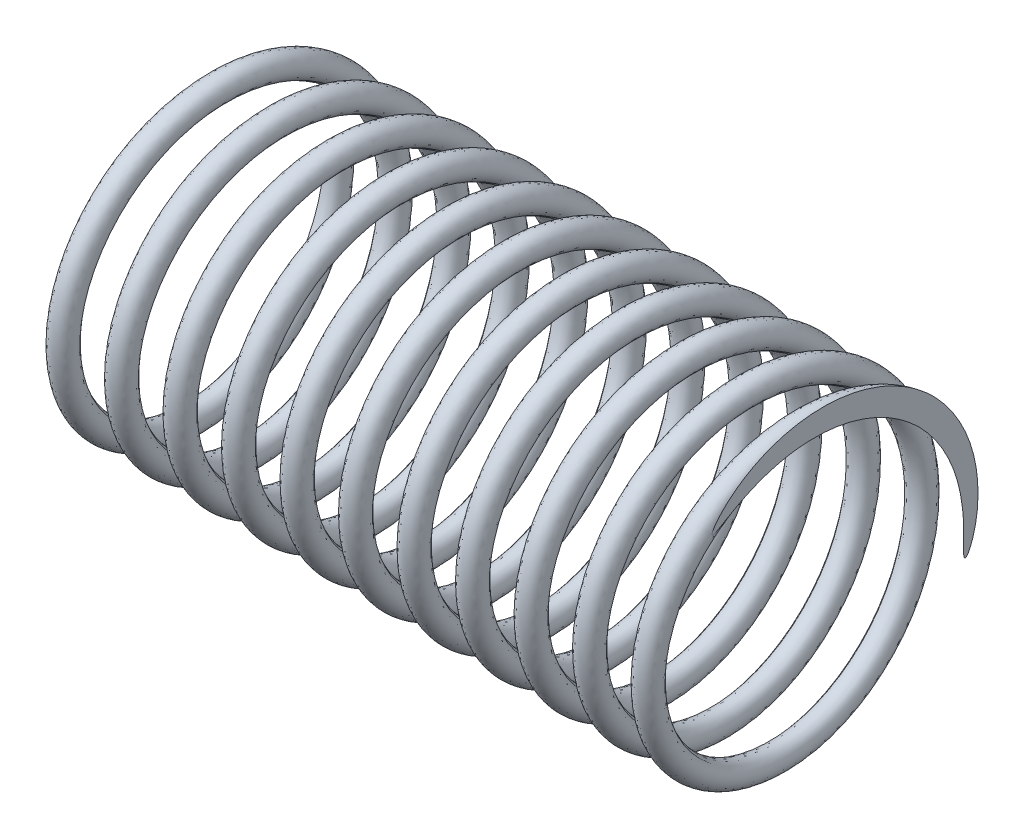
SolidWorks part; units mm, degrees
note: '?' marks a value the reader was unsure of.
material "SPRING STEEL ASTM A 229"
ref_plane "Front Plane" through (0, 0, 0) normal (0, 0, 1) x (1, 0, 0)
ref_plane "Top Plane" through (0, 0, 0) normal (0, 1, 0) x (1, 0, 0)
ref_plane "Right Plane" through (0, 0, 0) normal (1, 0, 0) x (0, 0, -1)
sketch "Sketch1" plane through (0, 0, 0) normal (1, 0, 0) x (0, 0, -1)
  circle A0 centre (0, 0) radius 3.1
  dimension "D1" = 6.2
curve "Helix/Spiral1" pitch 1.2 height 26 turns 21.6667
sketch "Sketch2" plane through (0, 0, 0) normal (0, 1, 0) x (1, 0, 0)
  circle A0 centre (0, 3.1) radius 0.25
  spline S0 degree 3 poles (0, 3.1) (0.0249, 3.1) (0.0752, 2.938) (0.1503, 2.2459) (0.2254, 1.2106) (0.3006, -0.0096) (0.3757, -1.2284) (0.4509, -2.2595) (0.526, -2.9453) (0.6012, -3.181) (0.6763, -2.9305) (0.7514, -2.2322) (0.8266, -1.1928) (0.9017, 0.0289) (0.9769, 1.2462) (1.052, 2.273) (1.1272, 2.9525) (1.2023, 3.1808) (1.2775, 2.923) (1.3526, 2.2185) (1.4277, 1.1749) (1.5029, -0.0481) (1.578, -1.2639) (1.6532, -2.2865) (1.7283, -2.9596) (1.8035, -3.1805) (1.8786, -2.9153) (1.9538, -2.2046) (2.0289, -1.157) (2.104, 0.0674) (2.1792, 1.2815) (2.2543, 2.2998) (2.3295, 2.9666) (2.4046, 3.1801) (2.4798, 2.9076) (2.5549, 2.1907) (2.6301, 1.1391) (2.7052, -0.0866) (2.7803, -1.2991) (2.8555, -2.3131) (2.9306, -2.9735) (3.0058, -3.1796) (3.0809, -2.8997) (3.1561, -2.1767) (3.2312, -1.1211) (3.3064, 0.1059) (3.3815, 1.3167) (3.4566, 2.3262) (3.5318, 2.9803) (3.6069, 3.1789) (3.6821, 2.8917) (3.7572, 2.1626) (3.8324, 1.103) (3.9075, -0.1251) (3.9827, -1.3342) (4.0578, -2.3393) (4.1329, -2.987) (4.2081, -3.1782) (4.2832, -2.8837) (4.3584, -2.1485) (4.4335, -1.085) (4.5087, 0.1444) (4.5838, 1.3516) (4.659, 2.3523) (4.7341, 2.9935) (4.8092, 3.1773) (4.8844, 2.8755) (4.9595, 2.1342) (5.0347, 1.0668) (5.1098, -0.1636) (5.185, -1.369) (5.2601, -2.3652) (5.3353, -3) (5.4104, -3.1763) (5.4855, -2.8672) (5.5607, -2.1199) (5.6358, -1.0487) (5.711, 0.1828) (5.7861, 1.3864) (5.8613, 2.3781) (5.9364, 3.0064) (6.0116, 3.1752) (6.0867, 2.8588) (6.1618, 2.1055) (6.237, 1.0305) (6.3121, -0.202) (6.3873, -1.4037) (6.4624, -2.3908) (6.5376, -3.0126) (6.6127, -3.174) (6.6879, -2.8503) (6.763, -2.0911) (6.8382, -1.0122) (6.9133, 0.2213) (6.9884, 1.4209) (7.0636, 2.4035) (7.1387, 3.0187) (7.2139, 3.1726) (7.289, 2.8417) (7.3642, 2.0765) (7.4393, 0.994) (7.5145, -0.2405) (7.5896, -1.4381) (7.6647, -2.4161) (7.7399, -3.0247) (7.815, -3.1712) (7.8902, -2.833) (7.9653, -2.0619) (8.0405, -0.9757) (8.1156, 0.2597) (8.1908, 1.4553) (8.2659, 2.4285) (8.341, 3.0306) (8.4162, 3.1696) (8.4913, 2.8242) (8.5665, 2.0472) (8.6416, 0.9573) (8.7168, -0.2788) (8.7919, -1.4724) (8.8671, -2.4409) (8.9422, -3.0364) (9.0173, -3.1679) (9.0925, -2.8153) (9.1676, -2.0324) (9.2428, -0.9389) (9.3179, 0.298) (9.3931, 1.4894) (9.4682, 2.4532) (9.5434, 3.0421) (9.6185, 3.1661) (9.6936, 2.8063) (9.7688, 2.0176) (9.8439, 0.9205) (9.9191, -0.3172) (9.9942, -1.5064) (10.0694, -2.4654) (10.1445, -3.0477) (10.2197, -3.1642) (10.2948, -2.7971) (10.3699, -2.0026) (10.4451, -0.9021) (10.5202, 0.3363) (10.5954, 1.5233) (10.6705, 2.4776) (10.7457, 3.0532) (10.8208, 3.1622) (10.896, 2.7879) (10.9711, 1.9876) (11.0462, 0.8836) (11.1214, -0.3555) (11.1965, -1.5402) (11.2717, -2.4896) (11.3468, -3.0585) (11.422, -3.16) (11.4971, -2.7786) (11.5723, -1.9726) (11.6474, -0.8651) (11.7225, 0.3746) (11.7977, 1.557) (11.8728, 2.5015) (11.948, 3.0637) (12.0231, 3.1577) (12.0983, 2.7692) (12.1734, 1.9574) (12.2486, 0.8465) (12.3237, -0.3937) (12.3988, -1.5738) (12.474, -2.5134) (12.5491, -3.0689) (12.6243, -3.1554) (12.6994, -2.7596) (12.7746, -1.9422) (12.8497, -0.828) (12.9249, 0.4128) (13, 1.5905) (13.0751, 2.5251) (13.1503, 3.0739) (13.2254, 3.1529) (13.3006, 2.75) (13.3757, 1.9269) (13.4509, 0.8094) (13.526, -0.4319) (13.6012, -1.6072) (13.6763, -2.5368) (13.7514, -3.0788) (13.8266, -3.1502) (13.9017, -2.7403) (13.9769, -1.9116) (14.052, -0.7907) (14.1272, 0.451) (14.2023, 1.6237) (14.2775, 2.5484) (14.3526, 3.0836) (14.4277, 3.1475) (14.5029, 2.7305) (14.578, 1.8961) (14.6532, 0.772) (14.7283, -0.47) (14.8035, -1.6403) (14.8786, -2.5599) (14.9538, -3.0882) (15.0289, -3.1447) (15.104, -2.7205) (15.1792, -1.8806) (15.2543, -0.7534) (15.3295, 0.4891) (15.4046, 1.6567) (15.4798, 2.5712) (15.5549, 3.0928) (15.6301, 3.1417) (15.7052, 2.7105) (15.7803, 1.8651) (15.8555, 0.7346) (15.9306, -0.5081) (16.0058, -1.6731) (16.0809, -2.5825) (16.1561, -3.0972) (16.2312, -3.1386) (16.3064, -2.7004) (16.3815, -1.8494) (16.4566, -0.7159) (16.5318, 0.5271) (16.6069, 1.6895) (16.6821, 2.5937) (16.7572, 3.1016) (16.8324, 3.1354) (16.9075, 2.6901) (16.9827, 1.8337) (17.0578, 0.6971) (17.1329, -0.5461) (17.2081, -1.7058) (17.2832, -2.6048) (17.3584, -3.1058) (17.4335, -3.1321) (17.5087, -2.6798) (17.5838, -1.818) (17.659, -0.6783) (17.7341, 0.565) (17.8092, 1.722) (17.8844, 2.6158) (17.9595, 3.1099) (18.0347, 3.1287) (18.1098, 2.6694) (18.185, 1.8021) (18.2601, 0.6595) (18.3353, -0.584) (18.4104, -1.7382) (18.4855, -2.6267) (18.5607, -3.1139) (18.6358, -3.1252) (18.711, -2.6589) (18.7861, -1.7862) (18.8613, -0.6406) (18.9364, 0.6029) (19.0116, 1.7543) (19.0867, 2.6375) (19.1618, 3.1178) (19.237, 3.1215) (19.3121, 2.6483) (19.3873, 1.7703) (19.4624, 0.6218) (19.5376, -0.6218) (19.6127, -1.7703) (19.6879, -2.6483) (19.763, -3.1215) (19.8382, -3.1178) (19.9133, -2.6375) (19.9884, -1.7543) (20.0636, -0.6029) (20.1387, 0.6406) (20.2139, 1.7862) (20.289, 2.6589) (20.3642, 3.1252) (20.4393, 3.1139) (20.5145, 2.6267) (20.5896, 1.7382) (20.6647, 0.584) (20.7399, -0.6595) (20.815, -1.8021) (20.8902, -2.6694) (20.9653, -3.1287) (21.0405, -3.1099) (21.1156, -2.6158) (21.1908, -1.722) (21.2659, -0.565) (21.341, 0.6783) (21.4162, 1.818) (21.4913, 2.6798) (21.5665, 3.1321) (21.6416, 3.1058) (21.7168, 2.6048) (21.7919, 1.7058) (21.8671, 0.5461) (21.9422, -0.6971) (22.0173, -1.8337) (22.0925, -2.6901) (22.1676, -3.1354) (22.2428, -3.1016) (22.3179, -2.5937) (22.3931, -1.6895) (22.4682, -0.5271) (22.5434, 0.7159) (22.6185, 1.8494) (22.6936, 2.7004) (22.7688, 3.1386) (22.8439, 3.0972) (22.9191, 2.5825) (22.9942, 1.6731) (23.0694, 0.5081) (23.1445, -0.7346) (23.2197, -1.8651) (23.2948, -2.7105) (23.3699, -3.1417) (23.4451, -3.0928) (23.5202, -2.5712) (23.5954, -1.6567) (23.6705, -0.4891) (23.7457, 0.7534) (23.8208, 1.8806) (23.896, 2.7205) (23.9711, 3.1447) (24.0462, 3.0882) (24.1214, 2.5599) (24.1965, 1.6403) (24.2717, 0.47) (24.3468, -0.772) (24.422, -1.8961) (24.4971, -2.7305) (24.5723, -3.1475) (24.6474, -3.0836) (24.7225, -2.5484) (24.7977, -1.6237) (24.8728, -0.451) (24.948, 0.7907) (25.0231, 1.9116) (25.0983, 2.7403) (25.1734, 3.1502) (25.2486, 3.0788) (25.3237, 2.5368) (25.3988, 1.6072) (25.474, 0.4319) (25.5491, -0.8093) (25.6243, -1.9269) (25.6994, -2.75) (25.7746, -3.1529) (25.8497, -3.0736) (25.9248, -2.5262) (25.9751, -1.8998) (26, -1.55) knots 0 0 0 0 0.00289 0.00578 0.008671 0.011561 0.014451 0.017341 0.020231 0.023121 0.026012 0.028902 0.031792 0.034682 0.037572 0.040462 0.043353 0.046243 0.049133 0.052023 0.054913 0.057803 0.060694 0.063584 0.066474 0.069364 0.072254 0.075145 0.078035 0.080925 0.083815 0.086705 0.089595 0.092486 0.095376 0.098266 0.101156 0.104046 0.106936 0.109827 0.112717 0.115607 0.118497 0.121387 0.124277 0.127168 0.130058 0.132948 0.135838 0.138728 0.141618 0.144509 0.147399 0.150289 0.153179 0.156069 0.15896 0.16185 0.16474 0.16763 0.17052 0.17341 0.176301 0.179191 0.182081 0.184971 0.187861 0.190751 0.193642 0.196532 0.199422 0.202312 0.205202 0.208092 0.210983 0.213873 0.216763 0.219653 0.222543 0.225434 0.228324 0.231214 0.234104 0.236994 0.239884 0.242775 0.245665 0.248555 0.251445 0.254335 0.257225 0.260116 0.263006 0.265896 0.268786 0.271676 0.274566 0.277457 0.280347 0.283237 0.286127 0.289017 0.291908 0.294798 0.297688 0.300578 0.303468 0.306358 0.309249 0.312139 0.315029 0.317919 0.320809 0.323699 0.32659 0.32948 0.33237 0.33526 0.33815 0.34104 0.343931 0.346821 0.349711 0.352601 0.355491 0.358382 0.361272 0.364162 0.367052 0.369942 0.372832 0.375723 0.378613 0.381503 0.384393 0.387283 0.390173 0.393064 0.395954 0.398844 0.401734 0.404624 0.407514 0.410405 0.413295 0.416185 0.419075 0.421965 0.424855 0.427746 0.430636 0.433526 0.436416 0.439306 0.442197 0.445087 0.447977 0.450867 0.453757 0.456647 0.459538 0.462428 0.465318 0.468208 0.471098 0.473988 0.476879 0.479769 0.482659 0.485549 0.488439 0.491329 0.49422 0.49711 0.5 0.50289 0.50578 0.508671 0.511561 0.514451 0.517341 0.520231 0.523121 0.526012 0.528902 0.531792 0.534682 0.537572 0.540462 0.543353 0.546243 0.549133 0.552023 0.554913 0.557803 0.560694 0.563584 0.566474 0.569364 0.572254 0.575145 0.578035 0.580925 0.583815 0.586705 0.589595 0.592486 0.595376 0.598266 0.601156 0.604046 0.606936 0.609827 0.612717 0.615607 0.618497 0.621387 0.624277 0.627168 0.630058 0.632948 0.635838 0.638728 0.641618 0.644509 0.647399 0.650289 0.653179 0.656069 0.65896 0.66185 0.66474 0.66763 0.67052 0.67341 0.676301 0.679191 0.682081 0.684971 0.687861 0.690751 0.693642 0.696532 0.699422 0.702312 0.705202 0.708092 0.710983 0.713873 0.716763 0.719653 0.722543 0.725434 0.728324 0.731214 0.734104 0.736994 0.739884 0.742775 0.745665 0.748555 0.751445 0.754335 0.757225 0.760116 0.763006 0.765896 0.768786 0.771676 0.774566 0.777457 0.780347 0.783237 0.786127 0.789017 0.791908 0.794798 0.797688 0.800578 0.803468 0.806358 0.809249 0.812139 0.815029 0.817919 0.820809 0.823699 0.82659 0.82948 0.83237 0.83526 0.83815 0.84104 0.843931 0.846821 0.849711 0.852601 0.855491 0.858382 0.861272 0.864162 0.867052 0.869942 0.872832 0.875723 0.878613 0.881503 0.884393 0.887283 0.890173 0.893064 0.895954 0.898844 0.901734 0.904624 0.907514 0.910405 0.913295 0.916185 0.919075 0.921965 0.924855 0.927746 0.930636 0.933526 0.936416 0.939306 0.942197 0.945087 0.947977 0.950867 0.953757 0.956647 0.959538 0.962428 0.965318 0.968208 0.971098 0.973988 0.976879 0.979769 0.982659 0.985549 0.988439 0.991329 0.99422 0.99711 1 1 1 1 construction
  dimension "D1" = 0.5
sweep "Sweep1" add profiles "Sketch2" path "Helix/Spiral1"
sketch "Sketch3" plane through (0, 0, 0) normal (0, 0, 1) x (1, 0, 0)
  line L0 (0, 0) -> (28.1754, 0) construction
  line L1 (58, 6.4802) -> (13, 6.4802)
  line L2 (58, 6.4802) -> (58, -6.4802)
  line L3 (58, -6.4802) -> (13, -6.4802)
  line L4 (13, 6.4802) -> (13, -6.4802)
  line L5 (0, 4.7829) -> (-1.4284, 4.7829)
  line L6 (0, 4.7829) -> (0, -6.4802)
  line L7 (0, -6.4802) -> (-1.4284, -6.4802)
  line L8 (-1.4284, 4.7829) -> (-1.4284, -6.4802)
  dimension "D1" = 11.2631
  dimension "D2" = 1.4284
  dimension "D3" = 4.7829
  dimension "D4" = 45
  dimension "D5" = 13
  dimension "D6" = 12.9605
extrude "Cut-Extrude1" cut sketch "Sketch3" against normal through all and the other way through all
ref_axis "Axis1" through (-1.7699, 0, 0) along (1, 0, 0)?
